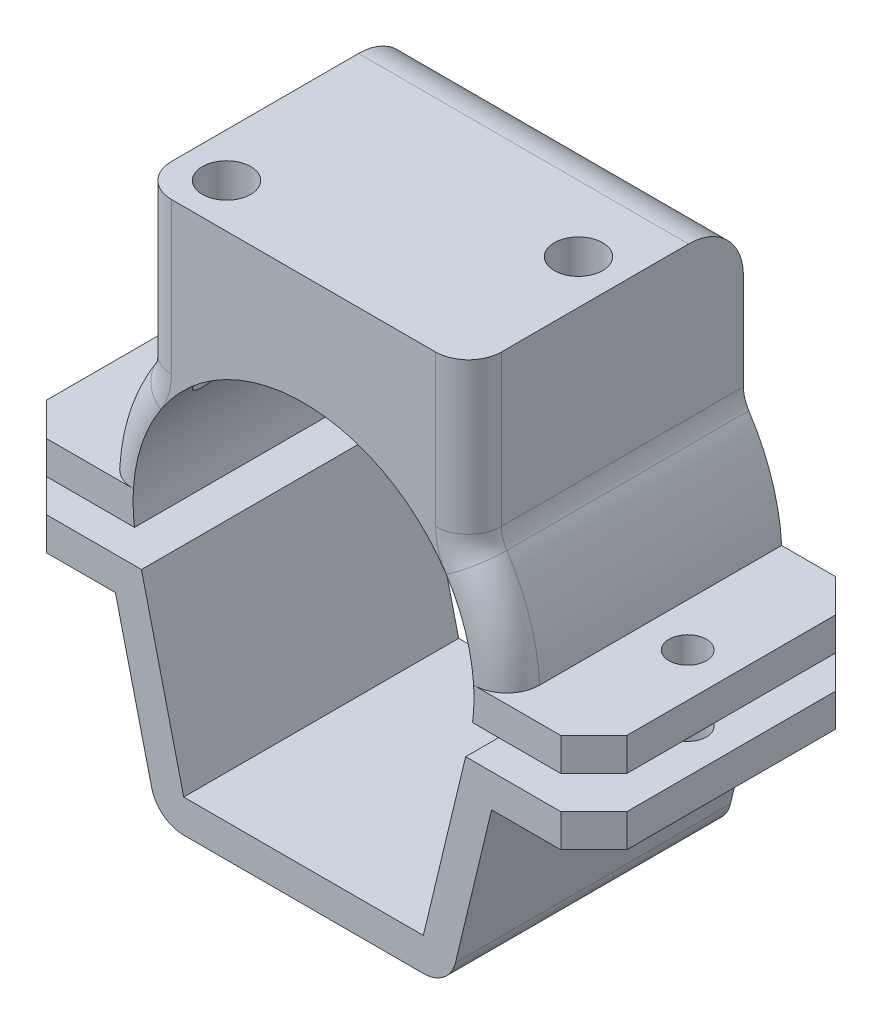
SolidWorks part; units mm, degrees
material "PET"
ref_plane "Front Plane" through (0, 0, 0) normal (0, 0, 1) x (1, 0, 0)
ref_plane "Top Plane" through (0, 0, 0) normal (0, 1, 0) x (1, 0, 0)
ref_plane "Right Plane" through (0, 0, 0) normal (1, 0, 0) x (0, 0, -1)
sketch "Sketch2" plane through (0, 0, 0) normal (0, 0, 1) x (1, 0, 0)
  line L0 (14.5846, -3.5054) -> (10.5, -20.5) construction
  line L1 (-14.5846, -3.5054) -> (14.5846, -3.5054) construction
  line L2 (-15.0708, -3.6223) -> (-10.8941, -21)
  line L3 (-14.5846, -3.5054) -> (-10.5, -20.5) construction
  line L4 (-10.5, -20.5) -> (10.5, -20.5) construction
  line L5 (-10.8941, -21) -> (10.8941, -21)
  line L6 (15.0708, -3.6223) -> (10.8941, -21)
  line L7 (0, 20.8065) -> (0, -39.2051) construction
  line L8 (-17.9877, -4.3234) -> (-17.8238, -5.0054)
  line L10 (17.9877, -4.3234) -> (17.8238, -5.0054)
  line L11 (-18.391, -2.0054) -> (18.391, -2.0054)
  line L20 (-17.8238, -5.0054) -> (-14.7384, -5.0054)
  line L21 (14.7384, -5.0054) -> (17.8238, -5.0054)
  line L22 (-17.8238, -5.0054) -> (-14.7384, -5.0054)
  line L23 (-17.8238, -5.0054) -> (-17.8238, -31)
  line L24 (-17.8238, -31) -> (17.8238, -31)
  line L25 (17.8238, -5.0054) -> (17.8238, -31)
  line L26 (14.7384, -5.0054) -> (17.8238, -5.0054)
  line L27 (-17.9877, -4.3234) -> (-13.2584, -24) construction
  line L28 (17.9877, -4.3234) -> (13.2584, -24) construction
  line L29 (-13.2584, -24) -> (13.2584, -24) construction
  line L30 (-17.8238, -5.0054) -> (-13.2584, -24)
  line L31 (15, 25.5) -> (-15, 25.5)
  line L32 (15, 25.5) -> (15, 10.8282)
  line L34 (-15, 25.5) -> (-15, 10.8282)
  line L35 (15, 25.5) -> (-7.0127, 17.9876) construction
  line L36 (1.3962, 19.9044) -> (-15, 25.5) construction
  line L37 (-13.2584, -24) -> (13.2584, -24)
  line L38 (17.8238, -5.0054) -> (13.2584, -24)
  arc A0 (14.5846, -3.5054) -> (-14.5846, -3.5054) centre (0, 0) ccw construction
  arc A1 (15.0708, -3.6223) -> (-15.0708, -3.6223) centre (0, 0) ccw
  arc A2 (17.9877, -4.3234) -> (15, 10.8282) centre (0, 0) ccw
  arc A3 (-15, 10.8282) -> (-17.9877, -4.3234) centre (0, 0) ccw
  arc A4 (17.9877, -4.3234) -> (-17.9877, -4.3234) centre (0, 0) ccw construction
  point P21 (0, -2.0054)
  point P24 (0, -6.0054)
  point P28 (0, 20.3809)
  point P39 (0, -24)
  dimension "D1" = 21
  dimension "D2" = 35.5
  dimension "D3" = 15
  dimension "D6" = 3
  dimension "D7" = 3
  dimension "D8" = 10
  dimension "D9" = 30
  dimension "D10" = 10
  dimension "D11" = 3
  dimension "D4" = 0.5
  dimension "D5" = 3
extrude "Boss-Extrude1" add sketch "Sketch2" along normal mid plane 25 contours L11 A2 A1 | L20 L8 L10 L6 L5 L2 region at (-13.209, -13.0971, 0) region at (0, 16.5571, 0)
sketch "Sketch9" plane through (0, 0, 0) normal (0, 0, 1) x (1, 0, 0)
  line L0 (17.8238, -5.0054) -> (13.2584, -24) construction
  line L1 (17.1027, -8.0054) -> (26.391, -8.0054)
  line L2 (17.1027, -8.0054) -> (17.1027, 0.9946)
  line L3 (17.1027, 0.9946) -> (26.391, 0.9946)
  line L4 (26.391, -8.0054) -> (26.391, 0.9946)
  line L5 (15.3697, -2.0054) -> (18.391, -2.0054) construction
  line L6 (-17.8238, -5.0054) -> (-14.7384, -5.0054) construction
  line L7 (18.391, 3.7065) -> (18.391, -6.8892) construction
  line L8 (17.1027, -2.0054) -> (26.391, -2.0054)
  line L9 (17.1027, -5.0054) -> (26.391, -5.0054)
  line L10 (0, -55) -> (0, 55) construction
  line L11 (-18.391, 3.7065) -> (-18.391, -6.8892) construction
  line L12 (-17.1027, -5.0054) -> (-26.391, -5.0054)
  line L13 (-17.1027, -2.0054) -> (-26.391, -2.0054)
  line L14 (-26.391, -8.0054) -> (-26.391, 0.9946)
  line L15 (-17.1027, 0.9946) -> (-26.391, 0.9946)
  line L16 (-17.1027, -8.0054) -> (-17.1027, 0.9946)
  line L17 (-17.1027, -8.0054) -> (-26.391, -8.0054)
  dimension "D1" = 3
  dimension "D2" = 3
  dimension "D3" = 8
extrude "Boss-Extrude4" add sketch "Sketch9" along normal up to surface (12.5 mm away) and the other way up to surface (12.5 mm away) contours L2 L8 L4 L3 | L9 L2 L1 L4 | L13 L16 L15 L14 | L17 L16 L12 L14 region at (21.7469, -6.5054, 0) region at (21.7469, -0.5054, 0) region at (-21.7469, -6.5054, 0) region at (-21.7469, -0.5054, 0) up to face at (0, 10.3462, 12.5) other way up to face at (0, -13.7527, -12.5)
sketch "Sketch12" plane through (0, 0.9946, 0) normal (0, 1, 0) x (1, 0, 0)
  line L0 (-26.391, 12.5) -> (-18.4732, -12.5) construction
  line L1 (-26.391, -12.5) -> (-18.4732, 12.5) construction
  line L2 (26.391, 12.5) -> (18.4732, -12.5) construction
  line L3 (26.391, 12.5) -> (18.4732, 12.5) construction
  line L4 (26.391, -12.5) -> (18.4732, 12.5) construction
  point P17 (-22.4321, 0)
  point P18 (22.4321, 0)
hole_wizard "M3 Clearance Hole1" positions "Sketch13" profile "Sketch14" hole size "M3" standard "ANSI Metric" end condition through all
sketch "Sketch13" plane through (0, 0.9946, 0) normal (0, 1, 0) x (1, 0, 0)
  line L0 (26.391, 12.5) -> (18.4732, -12.5) construction
  point P0 (-22.4321, 0)
  point P3 (22.4321, 0)
sketch "Sketch14" plane through (-22.4321, 0.9946, 0) normal (1, 0, 0) x (0, 0, 1)
  line L0 (0, 0) -> (0, 24.9946)
  line L1 (0, 24.9946) -> (1.7, 24.9946)
  line L2 (1.7, 24.9946) -> (1.7, 0)
  line L5 (1.7, 0) -> (0, 0)
  line L11 (0, -6.35) -> (0, 107.95) construction
  dimension "Thru Hole Dia." = 3.4
  dimension "Thru Hole Depth" = 24.9946
chamfer "Chamfer1" distance 3 angle 45 4 edges at (-26.391, -0.5054, -12.5) (26.391, -0.5054, -12.5) (26.391, -0.5054, 12.5) (-26.391, -0.5054, 12.5)
chamfer "Chamfer2" distance 3 angle 45 4 edges at (-26.391, -6.5054, -12.5) (-26.391, -6.5054, 12.5) (26.391, -6.5054, 12.5) (26.391, -6.5054, -12.5)
fillet "Fillet1" radius 3 2 edges at (13.2584, -24, 0) (-13.2584, -24, 0)
fillet "Fillet2" radius 3 2 edges at (15, 10.8282, 0) (-15, 10.8282, 0)
sketch "Sketch15" plane through (0, 25.5, 0) normal (0, 1, 0) x (1, 0, 0)
  line L0 (15, -12.5) -> (-15, -12.5) construction
  line L10 (0, -11.5) -> (0, 4.5) construction
  line L11 (14, -11.5) -> (-14, -11.5) construction
  line L12 (14, -11.5) -> (14, 4.5) construction
  line L13 (14, 4.5) -> (-14, 4.5) construction
  line L14 (-14, -11.5) -> (-14, 4.5) construction
  circle A0 centre (-11, -8.5) radius 2.2
  circle A1 centre (11, 1.5) radius 2.2
  dimension "D2" = 4.4
  dimension "D3" = 4.4
  dimension "D1" = 3
  dimension "D4" = 3
  dimension "D5" = 3
  dimension "D6" = 1
  dimension "D7" = 3
  dimension "D8" = 16
  dimension "D9" = 28
extrude "Cut-Extrude1" cut sketch "Sketch15" against normal up to next
fillet "Fillet3" radius 5 1 edges at (0, 25.5, -12.5)
fillet "Fillet4" radius 3 6 edges at (17.5828, 5.7529, 12.5) (15.1247, 10.9021, 12.5) (-17.5828, 5.7529, 12.5) (-15.1247, 10.9021, 12.5) (15, 18.629, 12.5) (-15, 18.629, 12.5)
